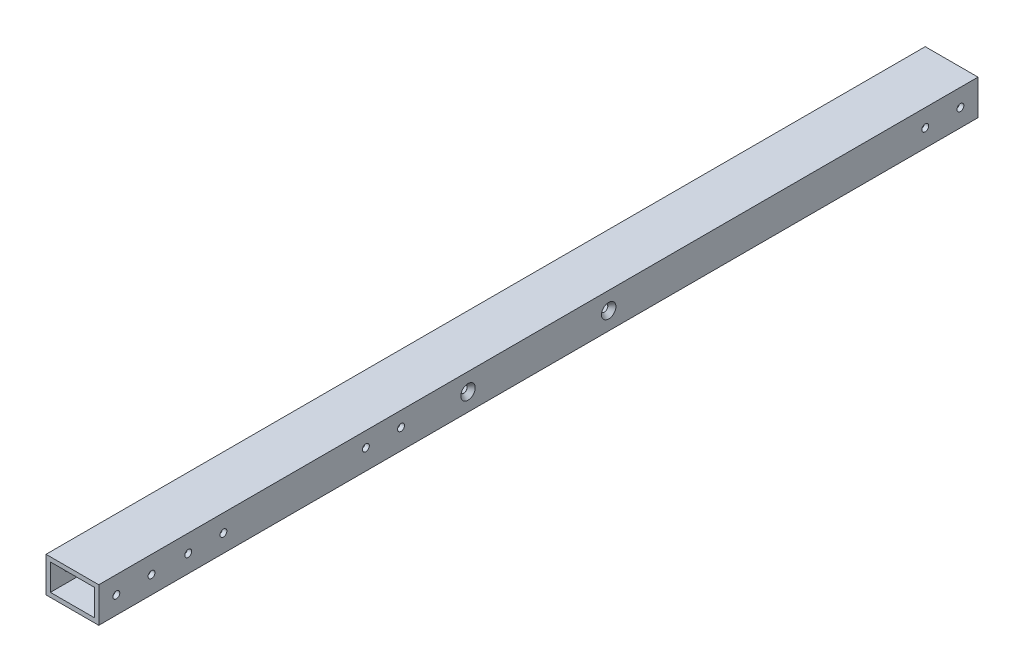
SolidWorks part; units mm, degrees
material "1060 Alloy"
ref_plane "Front Plane" through (0, 0, 0) normal (0, 0, 1) x (1, 0, 0)
ref_plane "Top Plane" through (0, 0, 0) normal (0, 1, 0) x (1, 0, 0)
ref_plane "Right Plane" through (0, 0, 0) normal (1, 0, 0) x (0, 0, -1)
sketch "Sketch1" plane through (0, 0, 0) normal (0, 0, 1) x (1, 0, 0)
  line L0 (-15.875, 9.525) -> (15.875, 9.525)
  line L2 (-19.05, 12.7) -> (19.05, 12.7)
  line L3 (-19.05, 12.7) -> (-19.05, -12.7)
  line L4 (-19.05, -12.7) -> (19.05, -12.7)
  line L5 (19.05, 12.7) -> (19.05, -12.7)
  line L10 (15.875, 9.525) -> (15.875, -9.525)
  line L11 (-15.875, -9.525) -> (15.875, -9.525)
  line L12 (-15.875, 9.525) -> (-15.875, -9.525)
  point P12 (0, 12.7)
  point P14 (19.05, 0)
  dimension "Wall Thickness" = 3.175
  dimension "Outside Width" = 38.1
  dimension "Outside Height" = 25.4
  dimension "Inside Height" = 19.05
  dimension "Inside Width" = 31.75
sketch "Sketch2" plane through (0, 0, 0) normal (1, 0, 0) x (0, 0, -1)
  line L0 (317.5, 0) -> (-317.5, 0)
  point P4 (0, 0)
  point P7 (-317.5, 0)
  point P10 (317.5, 0)
  dimension "Length" = 635
sketch "Sketch3" plane through (0, 0, 0) normal (0, 0, 1) x (1, 0, 0)
  line L21 (19.05, 12.7) -> (-19.05, 12.7)
  line L22 (19.05, -12.7) -> (19.05, 12.7)
  line L23 (-19.05, -12.7) -> (19.05, -12.7)
  line L24 (-19.05, 12.7) -> (-19.05, -12.7)
  line L25 (19.05, 12.7) -> (-19.05, 12.7)
  line L26 (19.05, -12.7) -> (19.05, 12.7)
  line L27 (-19.05, -12.7) -> (19.05, -12.7)
  line L28 (-19.05, 12.7) -> (-19.05, -12.7)
  line L29 (15.875, 9.525) -> (-15.875, 9.525)
  line L30 (15.875, -9.525) -> (15.875, 9.525)
  line L31 (-15.875, -9.525) -> (15.875, -9.525)
  line L32 (-15.875, 9.525) -> (-15.875, -9.525)
  line L33 (15.875, 9.525) -> (-15.875, 9.525)
  line L34 (15.875, -9.525) -> (15.875, 9.525)
  line L35 (-15.875, -9.525) -> (15.875, -9.525)
  line L36 (-15.875, 9.525) -> (-15.875, -9.525)
  dimension "D1" = 0
  dimension "D2" = 0
extrude "Boss-Extrude1" add sketch "Sketch3" along normal up to vertex (317.5 mm away) and the other way up to vertex (317.5 mm away) up to point (0, 0, 317.5) other way up to point (0, 0, -317.5)
sketch "Drawing Reference" plane through (0, 0, 0) normal (1, 0, 0) x (0, 0, -1)
  line L0 (-317.5, 0) -> (317.5, 0) construction
  line L1 (0, -12.7) -> (0, 12.7) construction
  line L2 (-317.5, -12.7) -> (317.5, -12.7) construction
  line L5 (-317.5, 12.7) -> (317.5, 12.7) construction
  point P7 (-290.068, 0)
  point P8 (290.068, 0)
  dimension "D1" = 27.432
sketch "Sketch4" plane through (-19.05, 0, 0) normal (-1, 0, 0) x (0, 0, 1)
  line L0 (-317.5, 0) -> (-304.8, 0)
  line L1 (-317.5, 12.7) -> (-317.5, -12.7) construction
  line L2 (-304.8, 0) -> (-279.4, 0)
  line L3 (317.5, 12.7) -> (317.5, -12.7) construction
  line L4 (317.5, 0) -> (304.8, 0)
  line L5 (304.8, 0) -> (279.4, 0)
  line L6 (0, 0) -> (50.8, 0) construction
  line L7 (0, 0) -> (-50.8, 0) construction
  point P11 (-304.8, 0)
  point P13 (-279.4, 0)
  point P14 (304.8, 0)
  point P15 (279.4, 0)
hole_wizard "#10 Clearance Hole2" positions "Sketch11" profile "Sketch12" hole size "#10" standard "ANSI Inch" end condition through all
sketch "Sketch11" plane through (-19.05, 0, 0) normal (-1, 0, 0) x (0, 0, 1)
  point P0 (-304.8, 0)
  point P3 (-279.4, 0)
  point P6 (279.4, 0)
  point P9 (304.8, 0)
sketch "Sketch12" plane through (-19.05, 0, -304.8) normal (0, 1, 0) x (0, 0, 1)
  line L0 (0, 0) -> (0, 38.1)
  line L1 (0, 38.1) -> (2.4892, 38.1)
  line L2 (2.4892, 38.1) -> (2.4892, 0)
  line L5 (2.4892, 0) -> (0, 0)
  line L11 (0, -6.35) -> (0, 107.95) construction
  dimension "Thru Hole Dia." = 4.9784
  dimension "Thru Hole Depth" = 38.1
hole_wizard "#10 Clearance Hole4" positions "Sketch14" profile "Sketch16" hole size "#10" standard "ANSI Inch" end condition through all
sketch "Sketch14" plane through (19.05, 0, 0) normal (1, 0, 0) x (0, 0, -1)
  point P33 (-252.857, 0)
  point P36 (-227.457, 0)
  point P42 (-124.587, 1.9434)
  point P45 (-99.187, 1.9434)
sketch "Sketch16" plane through (19.05, 0, 252.857) normal (0, 1, 0) x (0, 0, -1)
  line L0 (0, 0) -> (0, 38.1)
  line L1 (0, 38.1) -> (2.4892, 38.1)
  line L2 (2.4892, 38.1) -> (2.4892, 0)
  line L5 (2.4892, 0) -> (0, 0)
  line L11 (0, -6.35) -> (0, 107.95) construction
  dimension "Thru Hole Dia." = 4.9784
  dimension "Thru Hole Depth" = 38.1
sketch "Sketch17" plane through (19.05, 0, 0) normal (1, 0, 0) x (0, 0, -1)
  point P0 (-261.8407, 0)
  point P1 (-236.4407, 0)
hole_wizard "#10 Clearance Hole3" positions "Sketch20" profile "Sketch21" hole size "#10" standard "ANSI Inch" end condition through all
sketch "Sketch20" plane through (-19.05, 0, 0) normal (-1, 0, 0) x (0, 0, 1)
  point P0 (-50.8, 0)
  point P3 (50.8, 0)
sketch "Sketch21" plane through (-19.05, 0, -50.8) normal (0, 1, 0) x (0, 0, 1)
  line L0 (0, 0) -> (0, 38.1)
  line L1 (0, 38.1) -> (5.207, 38.1)
  line L2 (2.4892, 34.9735) -> (2.4892, 0)
  line L5 (2.4892, 0) -> (0, 0)
  line L7 (5.207, 38.1) -> (2.4892, 34.9735)
  line L8 (-5.207, 38.1) -> (-2.4892, 34.9735) construction
  line L11 (0, -6.35) -> (0, 107.95) construction
  dimension "Thru Hole Dia." = 4.9784
  dimension "Thru Hole Depth" = 38.1
  dimension "Far C'Sink Dia." = 10.414
  dimension "Far C'Sink Angle" = 82
equation "\"D1@Drawing Reference\"=\"Outside Width@Sketch1\" * 0.72"
